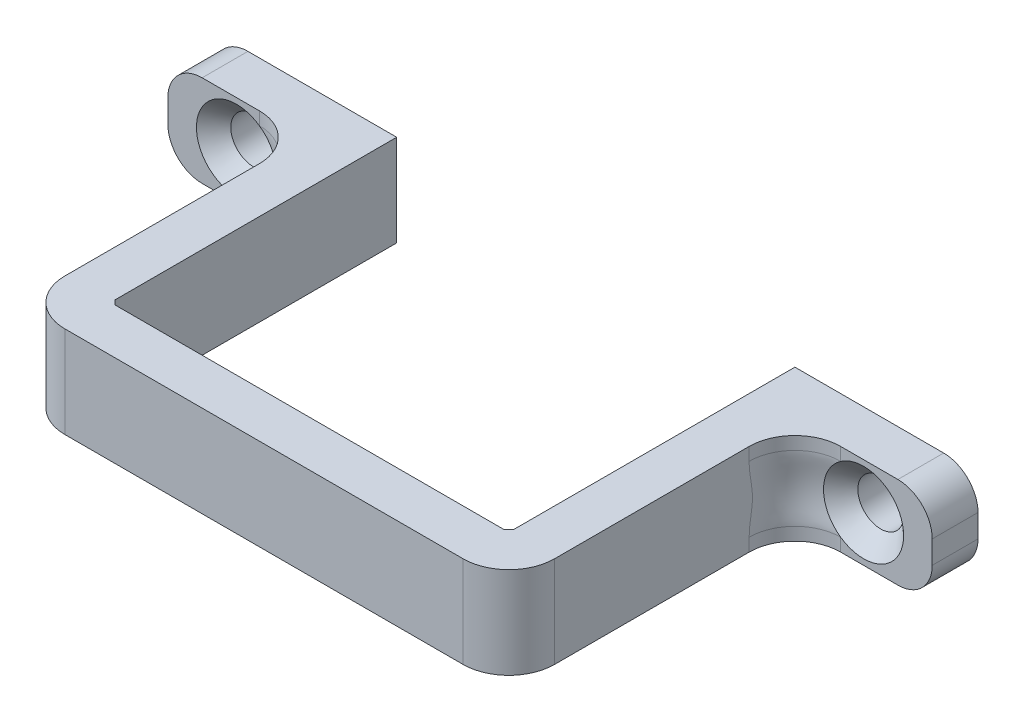
SolidWorks part; units mm, degrees
ref_plane "Front Plane" through (0, 0, 0) normal (0, 0, 1) x (1, 0, 0)
ref_plane "Top Plane" through (0, 0, 0) normal (0, 1, 0) x (1, 0, 0)
ref_plane "Right Plane" through (0, 0, 0) normal (1, 0, 0) x (0, 0, -1)
sketch "Sketch1" plane through (0, 0, 0) normal (0, 0, 1) x (1, 0, 0)
  line L1 (-17.4, 4) -> (17.4, 4)
  line L2 (-17.4, 4) -> (-17.4, -4)
  line L3 (-17.4, -4) -> (17.4, -4)
  line L4 (17.4, 4) -> (17.4, -4)
  line L5 (0, -4) -> (0, 4) construction
  line L6 (-17.4, 0) -> (17.4, 0) construction
  point P0 (0, 0)
  dimension "D1" = 8
  dimension "D2" = 34.8
extrude "Boss-Extrude1" add sketch "Sketch1" along normal blind 4
sketch "Sketch2" plane through (17.4, 0, 0) normal (1, 0, 0) x (0, 0, -1)
  line L0 (0, -4) -> (0, 4) construction
  line L1 (-4, 4) -> (25, 4)
  line L2 (-4, 4) -> (-4, -4)
  line L3 (-4, -4) -> (25, -4)
  line L4 (25, 4) -> (25, -4)
  dimension "D1" = 25
extrude "Boss-Extrude2" add sketch "Sketch2" along normal blind 4
sketch "Sketch4" plane through (0, 0, -25) normal (0, 0, -1) x (-1, 0, 0)
  line L1 (-17.4, 4) -> (-33.4, 4)
  line L2 (-17.4, 4) -> (-17.4, -4)
  line L3 (-17.4, -4) -> (-33.4, -4)
  line L4 (-33.4, 4) -> (-33.4, -4)
  line L5 (-21.4, -4) -> (-21.4, 4) construction
  circle A0 centre (-27.4, 0) radius 2
  point P10 (-27.4, 1.0333)
  point P11 (0, 0)
  dimension "D1" = 4
  dimension "D2" = 6
  dimension "D3" = 6
extrude "Boss-Extrude3" add sketch "Sketch4" against normal blind 4
mirror "Mirror1" about plane through (0, 0, 0) normal (1, 0, 0) of "Boss-Extrude3", "Boss-Extrude2"
chamfer "Chamfer1" distance 0.4 angle 45 2 edges at (17.4, 0, 0) (-17.4, 0, 0)
chamfer "Chamfer2" distance 1.5 angle 45 2 edges at (25.4, 0, -21) (-25.4, 0, -21)
fillet "Fillet1" radius 4 4 edges at (21.4, 0, 4) (-21.4, 0, 4) (21.4, 0, -21) (-21.4, 0, -21)
fillet "Fillet2" radius 3 4 edges at (33.4, 4, -23) (33.4, -4, -23) (-33.4, 4, -23) (-33.4, -4, -23)
